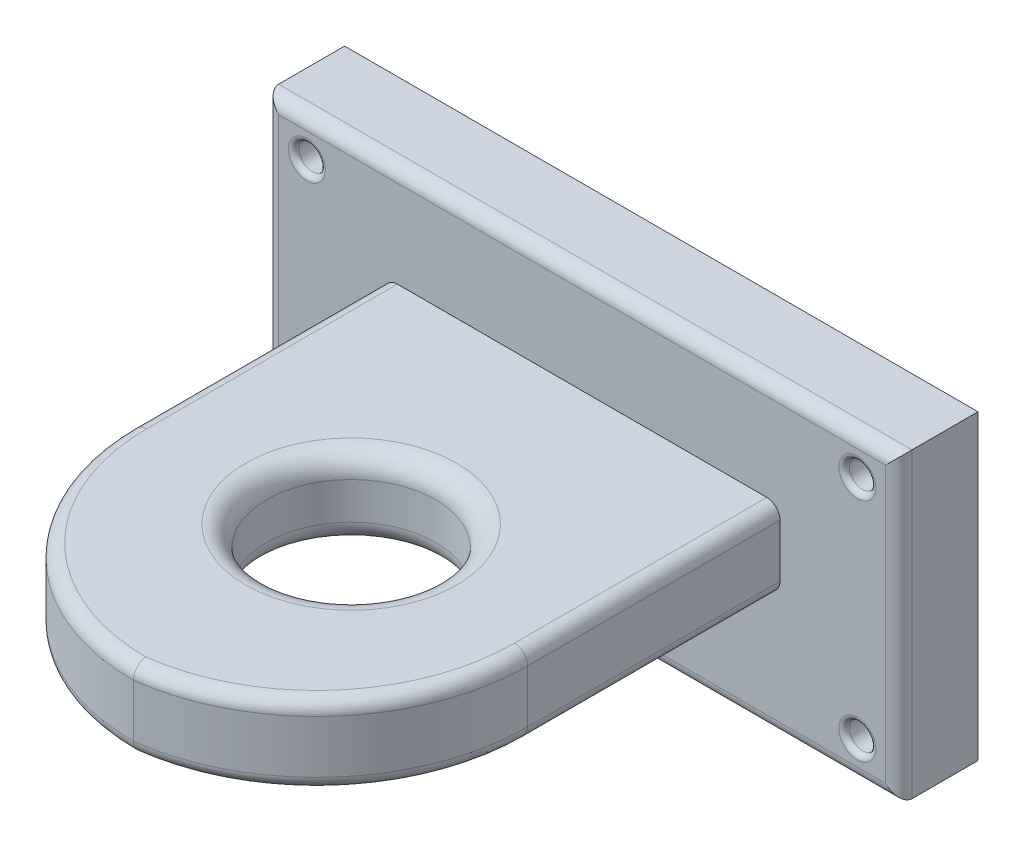
SolidWorks part; units mm, degrees
ref_plane "Front Plane" through (0, 0, 0) normal (0, 0, 1) x (1, 0, 0)
ref_plane "Top Plane" through (0, 0, 0) normal (0, 1, 0) x (1, 0, 0)
ref_plane "Right Plane" through (0, 0, 0) normal (1, 0, 0) x (0, 0, -1)
sketch "Sketch1" plane through (0, 0, 0) normal (0, 1, 0) x (1, 0, 0)
  line L1 (0, 0) -> (150, 0)
  line L2 (0, 0) -> (0, -175)
  line L3 (0, -175) -> (150, -175)
  line L4 (150, 0) -> (150, -175)
  dimension "D1" = 150
  dimension "D2" = 175
extrude "Boss-Extrude1" add sketch "Sketch1" along normal blind 30
sketch "Sketch3" plane through (0, 30, 0) normal (0, 1, 0) x (-1, 0, 0)
  circle A0 centre (-75, 87.5) radius 32
  dimension "D1" = 64
extrude "Cut-Extrude2" cut sketch "Sketch3" against normal through all
fillet "Fillet1" radius 80 1 edges at (0, 15, 175)
fillet "Fillet2" radius 80 1 edges at (150, 15, 175)
fillet "Fillet3" radius 8 1 edges at (75, 30, 119.5)
fillet "Fillet4" radius 8 1 edges at (75, 0, 119.5)
sketch "Sketch5" plane through (0, 0, 0) normal (0, 0, -1) x (-1, 0, 0)
  line L0 (-150, 30) -> (-150, 0) construction
  line L1 (-195, 68.1057) -> (45, 68.1057)
  line L2 (-195, 68.1057) -> (-195, -46.3609)
  line L3 (-195, -46.3609) -> (45, -46.3609)
  line L4 (45, 68.1057) -> (45, -46.3609)
  line L5 (-150, 30) -> (0, 30) construction
  line L6 (0, 30) -> (0, 0) construction
  dimension "D1" = 45
  dimension "D2" = 45
extrude "Boss-Extrude5" add sketch "Sketch5" along normal blind 30
fillet "Fillet5" radius 5 4 edges at (75, -46.3609, 0) (-45, 10.8724, 0) (75, 68.1057, 0) (195, 10.8724, 0)
fillet "Fillet6" radius 5 8 edges at (150, 0, 47.8137) (0, 0, 47.5) (23.4315, 0, 151.5685) (130, 0, 148.5425) (0, 30, 47.5) (150, 30, 47.8137) (23.4315, 30, 151.5685) (130, 30, 148.5425)
sketch "Sketch7" plane through (0, 0, 0) normal (0, 0, 1) x (1, 0, 0)
  line L0 (190, 10.8724) -> (-40, 10.8724) construction
  line L1 (190, -41.3609) -> (190, 63.1057) construction
  line L2 (-40, 63.1057) -> (-40, -41.3609) construction
  line L3 (75, -41.3609) -> (75, 63.1057) construction
  line L4 (-40, -41.3609) -> (190, -41.3609) construction
  line L5 (190, 63.1057) -> (-40, 63.1057) construction
  circle A0 centre (179.2714, 53.7421) radius 5
  circle A1 centre (179.2714, -31.9973) radius 5
  circle A2 centre (-29.2714, 53.7421) radius 5
  circle A3 centre (-29.2714, -31.9973) radius 5
extrude "Cut-Extrude3" cut sketch "Sketch7" against normal through all
fillet "Fillet7" radius 2 4 edges at (-24.2714, -31.9973, 0) (-34.2714, 53.7421, 0) (184.2714, 53.7421, 0) (174.2714, -31.9973, 0)
